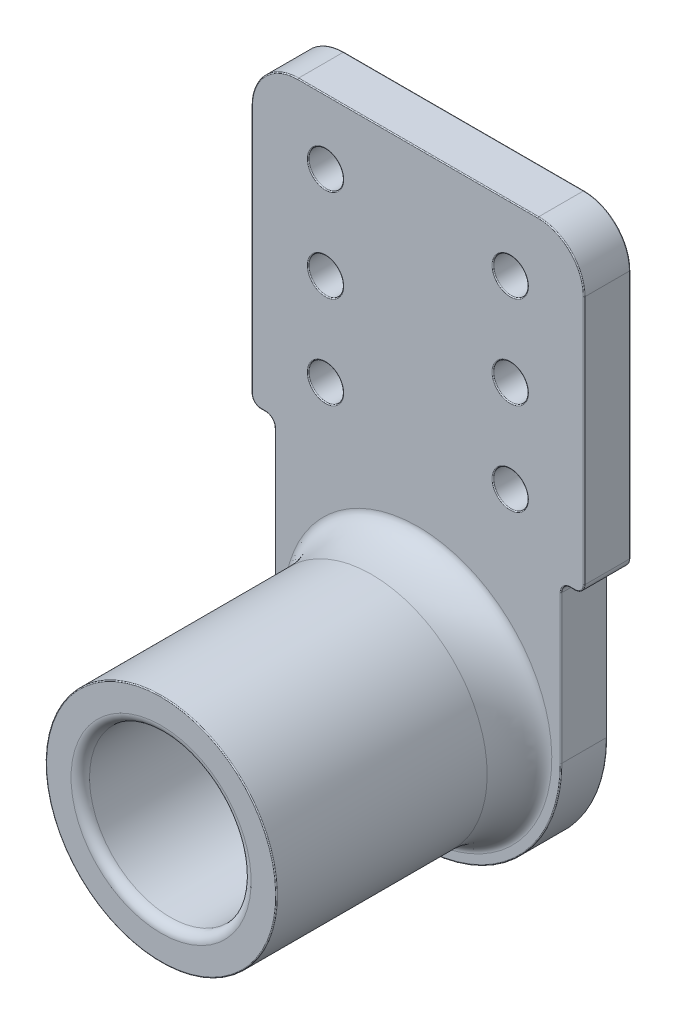
SolidWorks part; units mm, degrees
ref_plane "Front Plane" through (0, 0, 0) normal (0, 0, 1) x (1, 0, 0)
ref_plane "Top Plane" through (0, 0, 0) normal (0, 1, 0) x (1, 0, 0)
ref_plane "Right Plane" through (0, 0, 0) normal (1, 0, 0) x (0, 0, -1)
sketch "Sketch1" plane through (0, 0, 0) normal (1, 0, 0) x (0, 0, -1)
  line L0 (517.398, -15.875) -> (517.398, 15.875)
  line L1 (517.398, 15.875) -> (552.7038, 15.875)
  line L2 (552.7038, 15.875) -> (552.7038, -15.875)
  line L3 (552.7038, -15.875) -> (517.398, -15.875)
  line L4 (472.0361, 0) -> (442.3639, 0) construction
  line L5 (552.4498, 19.7485) -> (552.4498, 222.9485) construction
  line L6 (552.7038, -19.685) -> (559.0538, -19.685)
  line L7 (552.7038, -19.685) -> (552.7038, 60.325)
  line L8 (552.7038, 60.325) -> (559.0538, 60.325)
  line L9 (559.0538, -19.685) -> (559.0538, 60.325)
  point P3 (517.398, 0)
  point P14 (555.8788, 60.325)
  dimension "D1" = 31.75
  dimension "D2" = 6.35
  dimension "D3" = 0.254
  dimension "D4" = 3.81
  dimension "D5" = 44.45
sketch "Sketch2" plane through (0, 0, 0) normal (1, 0, 0) x (0, 0, -1)
  line L0 (552.7038, 15.875) -> (552.7038, -15.875) construction
  line L2 (517.398, -15.875) -> (517.398, 15.875) construction
  line L3 (552.7038, -15.875) -> (517.398, -15.875) construction
  line L4 (552.7038, 0) -> (552.7038, -15.875)
  line L6 (517.398, -15.875) -> (517.398, 0)
  line L7 (552.7038, -15.875) -> (517.398, -15.875)
  line L8 (552.7038, 0) -> (517.398, 0)
  point P6 (517.398, 0)
revolve "Revolve1" add sketch "Sketch2" angle 360 about L8
sketch "Sketch4" plane through (0, 0, -552.7038) normal (0, 0, -1) x (-1, 0, 0)
  line L1 (-19.685, 0) -> (19.685, 0) construction
  line L2 (-19.685, 0) -> (-19.685, 63.5)
  line L3 (-19.685, 63.5) -> (19.685, 63.5)
  line L4 (19.685, 0) -> (19.685, 63.5)
  arc A0 (19.685, 0) -> (-19.685, 0) centre (0, 0) cw
  dimension "D1" = 63.5
extrude "Boss-Extrude1" add sketch "Sketch4" along normal up to vertex (6.35 mm away) up to point (0, -19.685, -559.0538)
sketch "Sketch5" plane through (0, 0, -559.0538) normal (0, 0, -1) x (-1, 0, 0)
  circle A0 centre (0, 0) radius 11.1125
  dimension "D1" = 22.225
extrude "Cut-Extrude1" cut sketch "Sketch5" against normal through all both and the other way through all
sketch "Sketch6" plane through (0, 0, -559.0538) normal (0, 0, -1) x (-1, 0, 0)
  line L0 (-12.7, 123.118) -> (-12.7, 119.579) construction
  line L1 (-12.7, 29.21) -> (-12.7, 41.91) construction
  line L2 (-12.7, 41.91) -> (-12.7, 54.61) construction
  line L3 (19.685, 63.5) -> (-19.685, 63.5) construction
  circle A0 centre (-12.7, 29.21) radius 2.3813
  circle A1 centre (-12.7, 41.91) radius 2.3812
  circle A2 centre (-12.7, 54.61) radius 2.3812
  dimension "D2" = 4.7625
  dimension "D1" = 8.89
  dimension "D3" = 12.7
sketch "Sketch7" plane through (0, 0, -559.0538) normal (0, 0, -1) x (-1, 0, 0)
  line L0 (-19.685, 63.5) -> (-19.685, 0) construction
  line L1 (-19.685, 21.59) -> (-22.86, 21.59)
  line L2 (-19.685, 21.59) -> (-19.685, 63.5)
  line L3 (-19.685, 63.5) -> (-22.86, 63.5)
  line L4 (-22.86, 21.59) -> (-22.86, 63.5)
  line L6 (19.685, 63.5) -> (-19.685, 63.5) construction
  line L7 (0, 22.9107) -> (0, -22.9107) construction
  line L8 (19.685, 63.5) -> (22.86, 63.5)
  line L9 (22.86, 21.59) -> (22.86, 63.5)
  line L10 (19.685, 21.59) -> (22.86, 21.59)
  line L11 (19.685, 21.59) -> (19.685, 63.5)
  dimension "D1" = 41.91
  dimension "D2" = 3.175
extrude "Boss-Extrude2" add sketch "Sketch7" against normal up to surface (6.35 mm away) up to face at (0, 15.875, -552.7038)
sketch "Sketch8" plane through (0, 0, -559.0538) normal (0, 0, -1) x (-1, 0, 0)
  line L0 (0, 22.9107) -> (0, -22.9107) construction
  circle A0 centre (12.7, 54.61) radius 2.3812
  circle A1 centre (-12.7, 54.61) radius 2.3812
  circle A2 centre (-12.7, 54.61) radius 2.3812
  circle A3 centre (-12.7, 41.91) radius 2.3812
  circle A4 centre (-12.7, 41.91) radius 2.3812
  circle A5 centre (-12.7, 29.21) radius 2.3813
  circle A6 centre (-12.7, 29.21) radius 2.3813
  circle A7 centre (12.7, 41.91) radius 2.3812
  circle A8 centre (12.7, 29.21) radius 2.3813
  dimension "D1" = 0
  dimension "D2" = 0
  dimension "D3" = 0
extrude "Cut-Extrude2" cut sketch "Sketch8" against normal through all
fillet "Fillet1" radius 6.35 1 edges at (0, 15.875, -552.7038) second distance 2.54 first distance on face at (0, 15.875, -552.7038)
fillet "Fillet2" radius 1.27 4 edges at (-22.86, 21.59, -555.8788) (-19.685, 21.59, -555.8788) (22.86, 21.59, -555.8788) (19.685, 21.59, -555.8788)
fillet "Fillet3" radius 6.35 2 edges at (22.86, 63.5, -555.8788) (-22.86, 63.5, -555.8788)
fillet "Fillet4" radius 1.27 2 edges at (0, -11.1125, -559.0538) (0, 11.1125, -517.398)
fillet "Fillet5" radius 0.127 41 edges at (-21.0001, 61.6401, -559.0538) (-22.86, 40.005, -559.0538) (-22.488, 21.962, -559.0538) (-21.2725, 21.59, -559.0538) (-20.057, 21.218, -559.0538) (-19.685, 10.16, -559.0538) (0, -19.685, -559.0538) (19.685, 10.16, -559.0538) (20.057, 21.218, -559.0538) (21.2725, 21.59, -559.0538) (22.488, 21.962, -559.0538) (22.86, 40.005, -559.0538) (21.0001, 61.6401, -559.0538) (0, 63.5, -559.0538) (12.7, 56.9913, -559.0538) (-12.7, 26.8288, -559.0538) (-12.7, 39.5288, -559.0538) (-12.7, 52.2288, -559.0538) (12.7, 31.5913, -559.0538) (12.7, 44.2913, -559.0538) (22.488, 21.962, -552.7038) (21.2725, 21.59, -552.7038) (20.057, 21.218, -552.7038) (19.685, 10.16, -552.7038) (0, -19.685, -552.7038) (-19.685, 10.16, -552.7038) (-20.057, 21.218, -552.7038) (-21.2725, 21.59, -552.7038) (-22.488, 21.962, -552.7038) (-22.86, 40.005, -552.7038) (-21.0001, 61.6401, -552.7038) (0, 63.5, -552.7038) (21.0001, 61.6401, -552.7038) (22.86, 40.005, -552.7038) (12.7, 52.2288, -552.7038) (-12.7, 26.8288, -552.7038) (-12.7, 39.5288, -552.7038) (-12.7, 52.2288, -552.7038) (12.7, 26.8288, -552.7038) (12.7, 39.5288, -552.7038) (0, 15.875, -517.398)
